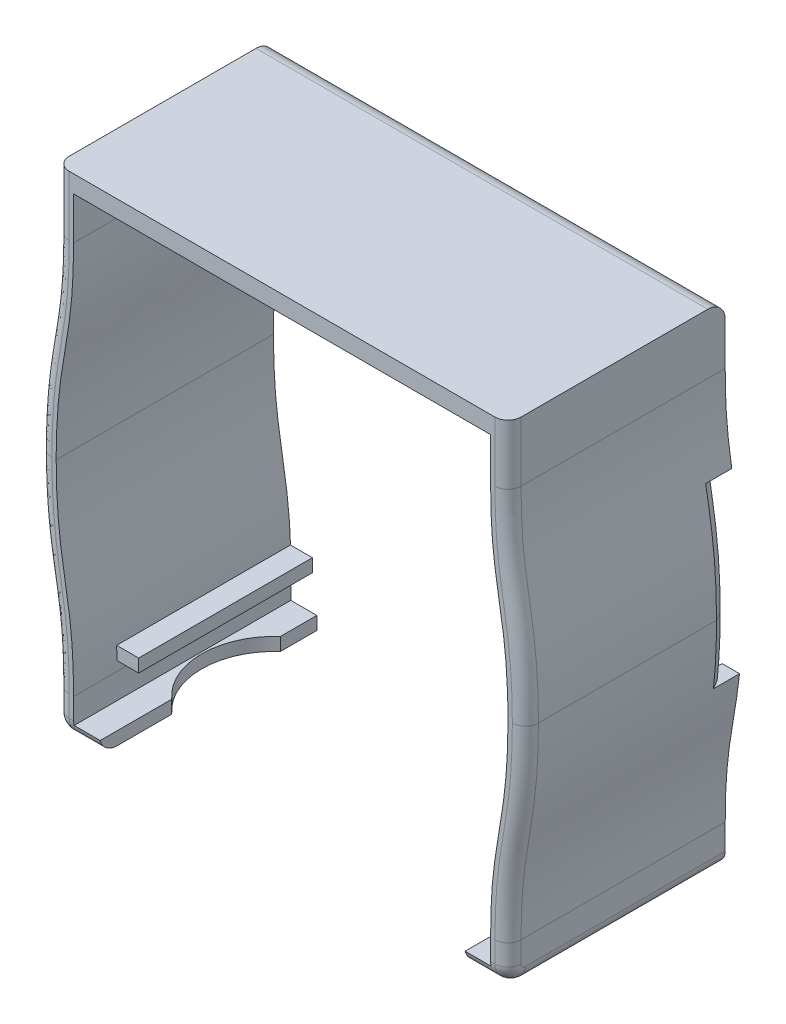
SolidWorks part; units mm, degrees
material "ABS"
ref_plane "Front Plane" through (0, 0, 0) normal (0, 0, 1) x (1, 0, 0)
ref_plane "Top Plane" through (0, 0, 0) normal (0, 1, 0) x (1, 0, 0)
ref_plane "Right Plane" through (0, 0, 0) normal (1, 0, 0) x (0, 0, -1)
sketch "Sketch1" plane through (0, 0, 0) normal (0, 0, 1) x (1, 0, 0)
  line L0 (26, 55.0198) -> (26, 53.0198)
  line L1 (26, 55.0198) -> (52, 55.0198)
  line L2 (50, 53.0198) -> (50, 48.125)
  line L3 (52, 0) -> (50, 0)
  line L4 (50, 2.9146) -> (50, 0)
  line L5 (50, 53.0198) -> (26, 53.0198)
  line L8 (52, 25.5198) -> (26, 25.5198) construction
  line L9 (52, 2.9146) -> (52, 0)
  line L10 (52, 55.0198) -> (52, 48.125)
  line L19 (52, 55.0198) -> (52, 48.125) construction
  line L20 (27.3097, 53.0198) -> (52, 53.0198) construction
  line L21 (5.2791, 2.5) -> (27.3097, 53.0198) construction
  line L22 (24, 2.5) -> (5.2791, 2.5) construction
  line L23 (24, 55.0198) -> (24, 2.5) construction
  line L24 (52, 55.0198) -> (24, 55.0198) construction
  line L25 (52, 2.9146) -> (52, 2) construction
  line L26 (52, 2) -> (52, 2) construction
  line L27 (26, 0.5) -> (2.2251, 0.5) construction
  line L28 (2.2251, 0.5) -> (26, 55.0198) construction
  line L29 (26, 53.0198) -> (26, 0.5) construction
  spline S0 degree 3 poles (50, 48.125) (50, 43.4006) (50.4927, 39.7147) (51.8357, 32.0632) (52, 27.7242) (52, 25.5198) knots 0 0 0 0 0.463728 0.673829 1 1 1 1
  spline S1 degree 3 poles (50, 2.9146) (50, 7.639) (50.4927, 11.3249) (51.8357, 18.9764) (52, 23.3154) (52, 25.5198) knots 0 0 0 0 0.463728 0.673829 1 1 1 1
  spline S2 degree 1 poles (52, 48.125) (54, 25.5198) knots 0 0 1 1 construction
  spline S3 degree 1 poles (52, 2.9146) (54, 25.5198) knots 0 0 1 1 construction
  spline S4 degree 3 poles (52, 48.125) (52, 47.823) (52.003, 47.2052) (52.0207, 46.0805) (52.0638, 44.7893) (52.1466, 43.4041) (52.2958, 41.7051) (52.5496, 39.7468) (52.9624, 37.2553) (53.4472, 34.3698) (53.7998, 31.2732) (53.9407, 28.762) (53.9925, 26.8474) (54, 25.9689) (54, 25.5198) knots 0 0 0 0 0.03125 0.0625 0.125 0.1875 0.25 0.375 0.5 0.625 0.75 0.875 0.9375 1 1 1 1
  spline S5 degree 3 poles (54, 25.5198) (54, 25.0707) (53.9925, 24.1922) (53.9407, 22.2776) (53.7998, 19.7664) (53.4472, 16.6698) (52.9624, 13.7843) (52.5496, 11.2928) (52.2958, 9.3345) (52.1466, 7.6355) (52.0638, 6.2503) (52.0207, 4.9591) (52.003, 3.8344) (52, 3.2166) (52, 2.9146) knots 0 0 0 0 0.0625 0.125 0.25 0.375 0.5 0.625 0.75 0.8125 0.875 0.9375 0.96875 1 1 1 1
  point P18 (52, 25.5198)
  point P31 (39, 55.0198)
  dimension "D1" = 2
  dimension "D2" = 29.5
  dimension "D4" = 24
  dimension "D6" = 2
  dimension "D7" = 2
extrude "Boss-Extrude1" add sketch "Sketch1" along normal blind 25
sketch "Sketch2" plane through (52, 0, 0) normal (1, 0, 0) x (0, 0, -1)
  line L3 (-25, 0) -> (0, 0) construction
  line L4 (-25, 0) -> (-25, 2.9146) construction
  line L5 (0, 0) -> (0, 2.9146) construction
  circle A0 centre (-23, 1.5) radius 1
  circle A1 centre (-2, 1.5) radius 1
  dimension "D1" = 2
  dimension "D2" = 2
  dimension "D5" = 1.5
  dimension "D6" = 2
  dimension "D3" = 1.5
  dimension "D4" = 2
extrude "Cut-Extrude1" [suppressed] cut sketch "Sketch2" against normal up to surface (2 mm away)
hole_wizard "M2 Clearance Hole1" [suppressed] positions "Sketch4" profile "Sketch5" hole size "M2" standard "ISO"
sketch "Sketch4" plane through (52, 0, 0) normal (1, 0, 0) x (0, 0, -1)
  line L0 (-10, 0) -> (0, 0) construction
  line L1 (-10, 0) -> (-10, 53) construction
  point P0 (-8, 1.5)
  dimension "D1" = 1.5
  dimension "D2" = 2
sketch "Sketch5" plane through (52, 1.5, 8) normal (0, 1, 0) x (0, 0, -1)
  line L0 (0, 0) -> (0, 50.72)
  line L1 (0, 50.72) -> (1.2, 49.999)
  line L2 (1.2, 49.999) -> (1.2, 0)
  line L5 (1.2, 0) -> (0, 0)
  line L10 (0, 50.72) -> (-1.2, 49.999) construction
  line L11 (0, -6.35) -> (0, 107.95) construction
  dimension "Hole Dia." = 2.4
  dimension "Hole Depth" = 49.999
  dimension "Drill Angle" = 118
ref_plane "Plane1" through (0, 0, 12.5) normal (0, 0, 1) x (1, 0, 0)
mirror "Mirror1" [suppressed] about plane through (0, 0, 12.5) normal (0, 0, 1)
ref_plane "Plane2" through (26, 0, 0) normal (-1, 0, 0) x (0, 0, 1)
mirror "Mirror2" [suppressed] about plane through (26, 0, 0) normal (-1, 0, 0)
fillet "Fillet2" [suppressed] radius 2
mirror "Mirror4" about plane through (26, 55.0198, 25) normal (1, 0, 0) of "Cut-Extrude1", "Boss-Extrude1"
fillet "Fillet6" radius 2 1 edges at (26, 55.0198, 0)
sketch "Sketch10" plane through (0, 0, 25) normal (0, 0, 1) x (1, 0, 0)
  line L1 (50.0392, 5.5) -> (47.5063, 5.5)
  line L2 (50, 0) -> (52, 0) construction
  line L3 (50.0063, 4) -> (47.5063, 4)
  line L4 (47.5063, 5.5) -> (47.5063, 4)
  spline S0 degree 3 poles (507.327, -2939.4543) (-5.912, 140.5178) (59.4027, 62.0894) (44.7193, -21.5686) (60.4923, 20.4375) (252.019, -2990.1547) knots -5.634594 -5.634594 -5.634594 -5.634594 0.326171 0.536272 5.298973 5.298973 5.298973 5.298973 only from (52, 25.5198) to (50, 2.9146) construction
  spline S1 degree 3 poles (50.0392, 5.5) (50.0135, 4.7098) (50, 3.8556) (50, 2.9146) knots 0.907636 0.907636 0.907636 0.907636 1 1 1 1
  spline M19 degree 3 poles (52, 25.5198) (52, 23.3154) (51.8357, 18.9764) (50.4927, 11.3249) (50, 7.639) (50, 2.9146) knots 0 0 0 0 0.326171 0.536272 1 1 1 1
  dimension "D1" = 4
  dimension "D2" = 1.5
  dimension "D3" = 2.5
extrude "Boss-Extrude7" add sketch "Sketch10" against normal up to surface (20 mm away) from offset 5 contours L1 L4 L3 M19 up to face at (51.4, 25.9158, 0) offset against normal yes
sketch "Sketch11" plane through (0, 0, 25) normal (0, 0, 1) x (1, 0, 0)
  line L1 (52, 0) -> (47, 0)
  line L2 (52, 0) -> (52, -1.5)
  line L3 (52, -1.5) -> (47, -1.5)
  line L4 (47, 0) -> (47, -1.5)
  dimension "D1" = 1.5
  dimension "D2" = 5
extrude "Boss-Extrude8" add sketch "Sketch11" against normal up to surface (25 mm away) up to face at (50.6458, 19.8149, 0)
fillet "Fillet7" [suppressed] radius 1.2
mirror "Mirror5" about plane through (26, 0, 0) normal (-1, 0, 0) of "Boss-Extrude7", "Boss-Extrude8"
fillet "Fillet9" radius 2 6 edges at (3.5, 0, 25) (5, -0.75, 25) (2.5, -1.5, 25) (48.5, 0, 25) (47, -0.75, 25) (49.5, -1.5, 25)
sketch "Sketch12" plane through (52, 0, 0) normal (1, 0, 0) x (0, 0, -1)
  line L0 (0, 25.5198) -> (0, 48.125) construction
  line L1 (0, 38.5198) -> (-2, 38.5198)
  line L2 (0, 38.5198) -> (0, 18.5198)
  line L3 (0, 18.5198) -> (-2, 18.5198)
  line L4 (-2, 38.5198) -> (-2, 18.5198)
  line L5 (-25, 55.0198) -> (-2, 55.0198) construction
  dimension "D1" = 20
  dimension "D2" = 16.5
  dimension "D3" = 2
extrude "Cut-Extrude5" cut sketch "Sketch12" against normal blind 2 and the other way blind 7
chamfer "Chamfer1" distance 1 angle 30 2 edges first distance on face at (52.9417, 13.0506, 9) first distance on face at (53.0441, 35.7873, 9)
sketch "Sketch13" plane through (0, -1.5, 0) normal (0, -1, 0) x (1, 0, 0)
  line L1 (47, 0) -> (47, 23) construction
  line L2 (47, 16.7) -> (47, 4.2)
  arc A0 (47, 4.2) -> (47, 16.7) centre (41.4246, 10.45) ccw
  point P3 (49.8, 10.45)
  point P6 (47, 10.45)
  dimension "D1" = 2.8
  dimension "D2" = 4.2
  dimension "D3" = 12.5
extrude "Cut-Extrude6" cut sketch "Sketch13" against normal up to surface (1.5 mm away) up to face at (48.5, 0, 12.4682)
mirror "Mirror6" about plane through (26, 0, 0) normal (-1, 0, 0) of "Cut-Extrude6"
fillet "Fillet10" radius 1.5 13 edges at (0, -1.5, 11.5) (0, 1.7073, 25) (0, -0.9142, 24.4142) (52, 1.7073, 25) (52, -0.9142, 24.4142) (0, 51.5724, 25) (52, 51.5724, 25) (52, -1.5, 11.5)
equation "\"D2@Sketch2\"=\"D1@Sketch2\""
